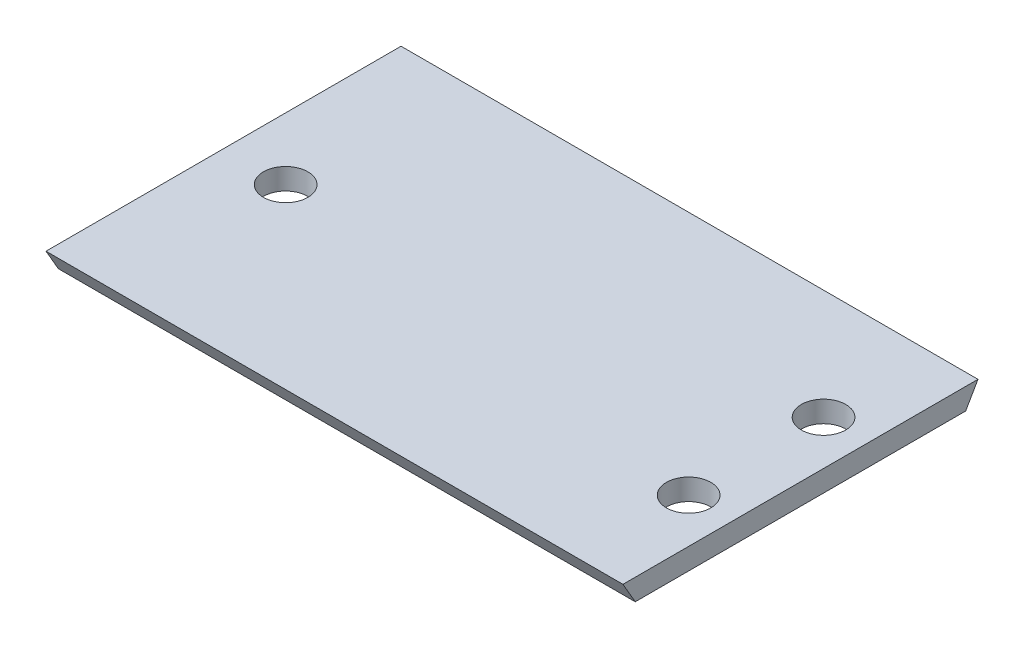
SolidWorks part; units mm, degrees
ref_plane "Front Plane" through (0, 0, 0) normal (0, 0, 1) x (1, 0, 0)
ref_plane "Top Plane" through (0, 0, 0) normal (0, 1, 0) x (1, 0, 0)
ref_plane "Right Plane" through (0, 0, 0) normal (1, 0, 0) x (0, 0, -1)
sketch "Sketch1" plane through (0, 0, 0) normal (0, 1, 0) x (1, 0, 0)
  line L0 (0, 0) -> (32.5, 0)
  line L1 (32.5, 0) -> (32.5, 20)
  line L2 (32.5, 20) -> (0, 20)
  line L3 (0, 20) -> (0, 0)
  line L4 (30, 0) -> (30, 20)
  line L8 (32.5, 10) -> (30, 10) construction
  line L9 (3.5, 20) -> (3.5, 0)
  circle A0 centre (30, 6.2) radius 1.25
  circle A1 centre (30, 13.8) radius 1.25
  circle A2 centre (3.5, 10) radius 1.25
  dimension "D5" = 2.5
  dimension "D8" = 2.5
  dimension "D1" = 2.5
  dimension "D2" = 20
  dimension "D3" = 3.5
  dimension "D4" = 30
  dimension "D6" = 3.8
  dimension "D7" = 3.8
extrude "Boss-Extrude1" add sketch "Sketch1" against normal blind 1.2
chamfer "Chamfer1" distance 1.2 angle 30 1 edges at (16.25, -1.2, -20)
chamfer "Chamfer2" distance 1.2 angle 30 1 edges at (16.25, -1.2, 0)
